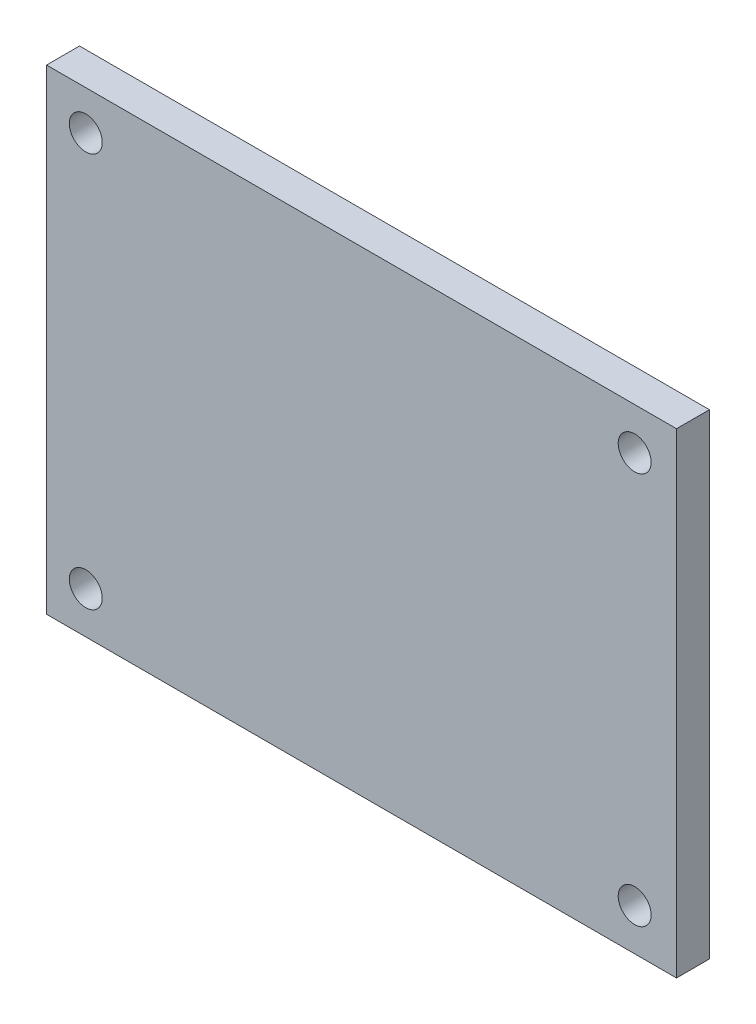
SolidWorks part; units mm, degrees
ref_plane "Plan de face" through (0, 0, 0) normal (0, 0, 1) x (1, 0, 0)
ref_plane "Plan de dessus" through (0, 0, 0) normal (0, 1, 0) x (1, 0, 0)
ref_plane "Plan de droite" through (0, 0, 0) normal (1, 0, 0) x (0, 0, -1)
sketch "Esquisse1" plane through (0, 0, 0) normal (0, 0, 1) x (1, 0, 0)
  line L1 (0, 0) -> (61.214, 0)
  line L2 (0, 0) -> (0, 46.228)
  line L3 (0, 46.228) -> (61.214, 46.228)
  line L4 (61.214, 0) -> (61.214, 46.228)
  dimension "D1" = 61.214
  dimension "D2" = 46.228
extrude "Boss.-Extru.1" add sketch "Esquisse1" along normal blind 3.2
sketch "Esquisse2" plane through (0, 0, 3.2) normal (0, 0, 1) x (1, 0, 0)
  line L0 (0, 0) -> (61.214, 0) construction
  line L1 (0, 46.228) -> (0, 0) construction
  line L2 (61.214, 46.228) -> (0, 46.228) construction
  line L3 (61.214, 0) -> (61.214, 46.228) construction
  circle A0 centre (3.81, 4.064) radius 1.6
  circle A1 centre (3.81, 42.418) radius 1.6
  circle A2 centre (57.15, 42.164) radius 1.6
  circle A3 centre (57.15, 4.064) radius 1.6
  dimension "D3" = 3.2
  dimension "D6" = 3.2
  dimension "D9" = 3.2
  dimension "D12" = 3.2
  dimension "D1" = 4.064
  dimension "D2" = 3.81
  dimension "D4" = 3.81
  dimension "D5" = 3.81
  dimension "D7" = 4.064
  dimension "D8" = 4.064
  dimension "D10" = 4.064
  dimension "D11" = 4.064
extrude "Enlèv. mat.-Extru.1" cut sketch "Esquisse2" against normal up to surface (3.2 mm away) up to face at (30.607, 23.114, 0)
sketch "Esquisse3" plane through (0, 0, 3.2) normal (0, 0, 1) x (1, 0, 0)
  text T0 "<b>Interface with actuators</b>"
